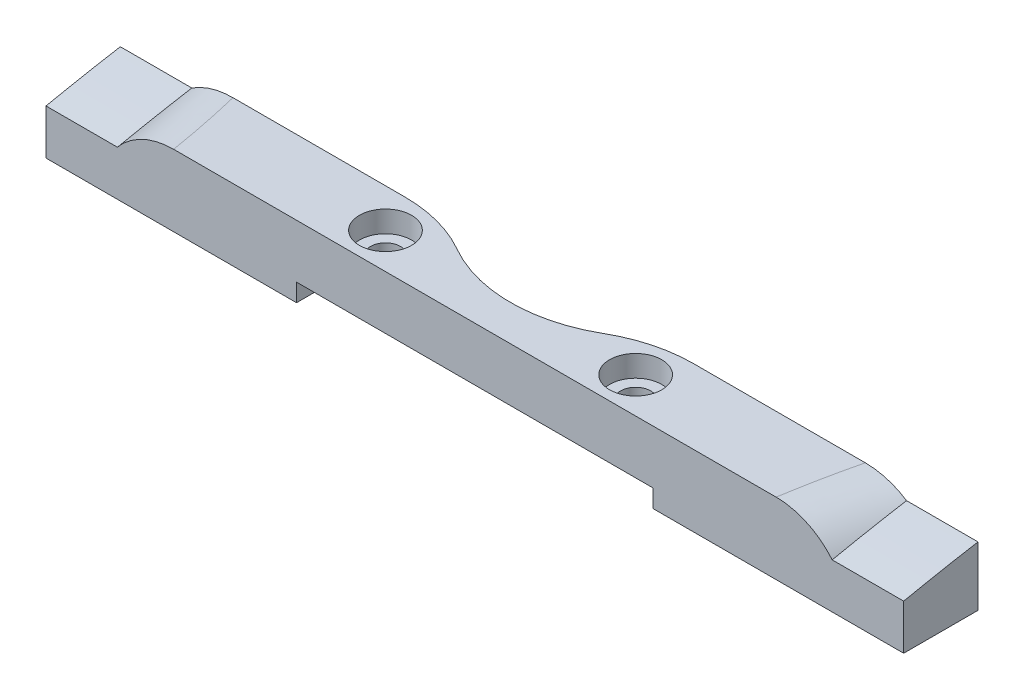
SolidWorks part; units mm, degrees
ref_plane "Ebene vorne" through (0, 0, 0) normal (0, 0, 1) x (1, 0, 0)
ref_plane "Ebene oben" through (0, 0, 0) normal (0, 1, 0) x (1, 0, 0)
ref_plane "Ebene rechts" through (0, 0, 0) normal (1, 0, 0) x (0, 0, -1)
sketch "Skizze1" plane through (0, 0, 0) normal (0, 1, 0) x (1, 0, 0)
  line L0 (-60, 0) -> (60, 0)
  line L1 (60, 0) -> (60, 10.4)
  line L2 (60, 10.4) -> (13.8609, 10.4)
  line L3 (0, 10) -> (0, 0) construction
  line L4 (-60, 0) -> (-60, 10.4)
  line L5 (-13.8609, 10.4) -> (-60, 10.4)
  arc A0 (13.8609, 10.4) -> (0, 5) centre (0, 25.4893) cw
  arc A1 (-13.8609, 10.4) -> (0, 5) centre (0, 25.4893) ccw
  dimension "D3" = 5
  dimension "D1" = 120
  dimension "D2" = 10.4
extrude "Aufsatz-Linear austragen1" add sketch "Skizze1" along normal blind 10
sketch "Skizze3" plane through (0, 10, 0) normal (0, 1, 0) x (1, 0, 0)
  line L0 (0, 0) -> (0, 22.3064) construction
  line L1 (17.5, 5) -> (-17.5, 5) construction
  line L2 (0, 13) -> (0, 5) construction
  circle A0 centre (17.5, 5) radius 2.1
  circle A1 centre (0, 13) radius 2.5 construction
  circle A2 centre (-17.5, 5) radius 2.1
  arc A3 (-13.8609, 10.4) -> (13.8609, 10.4) centre (0, 25.4893) ccw construction
  dimension "D1" = 4.2
  dimension "D4" = 5
  dimension "D2" = 35
  dimension "D3" = 8
  dimension "D5" = 8
extrude "Schnitt-Linear austragen1" cut sketch "Skizze3" against normal blind 10 contours A0 | A2 region at (17.5, 10, -5)
sketch "Skizze4" plane through (-60, 0, 0) normal (1, 0, 0) x (0, 0, -1)
  line L0 (0, 10) -> (10.4, 10)
  line L1 (10.4, 10) -> (10.4, 8.2965)
  line L2 (10.4, 10) -> (10.4, 0) construction
  line L3 (0, 10) -> (0, 6.32)
  line L4 (0, 10) -> (0, 0) construction
  arc A1 (0, 6.32) -> (10.4, 8.2965) centre (58.0172, -270.6068) cw
extrude "Schnitt-Linear austragen2" cut sketch "Skizze4" along normal blind 10
fillet "Verrundung1" radius 10 1 edges at (-50, 10, -5.2)
mirror "Spiegeln1" about plane through (0, 0, 0) normal (1, 0, 0) of "Schnitt-Linear austragen2", "Verrundung1"
sketch "Skizze5" plane through (0, 10, 0) normal (0, 1, 0) x (1, 0, 0)
  circle A0 centre (-17.5, 5) radius 3.65
  circle A1 centre (17.5, 5) radius 3.65
  dimension "D1" = 7.3
extrude "Schnitt-Linear austragen3" cut sketch "Skizze5" against normal blind 3
fillet "Verrundung2" radius 20 2 edges at (13.8609, 5, -10.4) (-13.8609, 5, -10.4)
sketch "Skizze6" plane through (0, 0, 0) normal (0, -1, 0) x (1, 0, 0)
  line L1 (-24.9478, 11.0453) -> (24.9478, 11.0453)
  line L2 (-24.9478, 11.0453) -> (-24.9478, -11.0453)
  line L3 (-24.9478, -11.0453) -> (24.9478, -11.0453)
  line L4 (24.9478, 11.0453) -> (24.9478, -11.0453)
  line L5 (-24.9478, 11.0453) -> (24.9478, -11.0453) construction
  line L6 (-24.9478, -11.0453) -> (24.9478, 11.0453) construction
  point P0 (0, 0)
extrude "Schnitt-Linear austragen4" cut sketch "Skizze6" against normal blind 2.5
